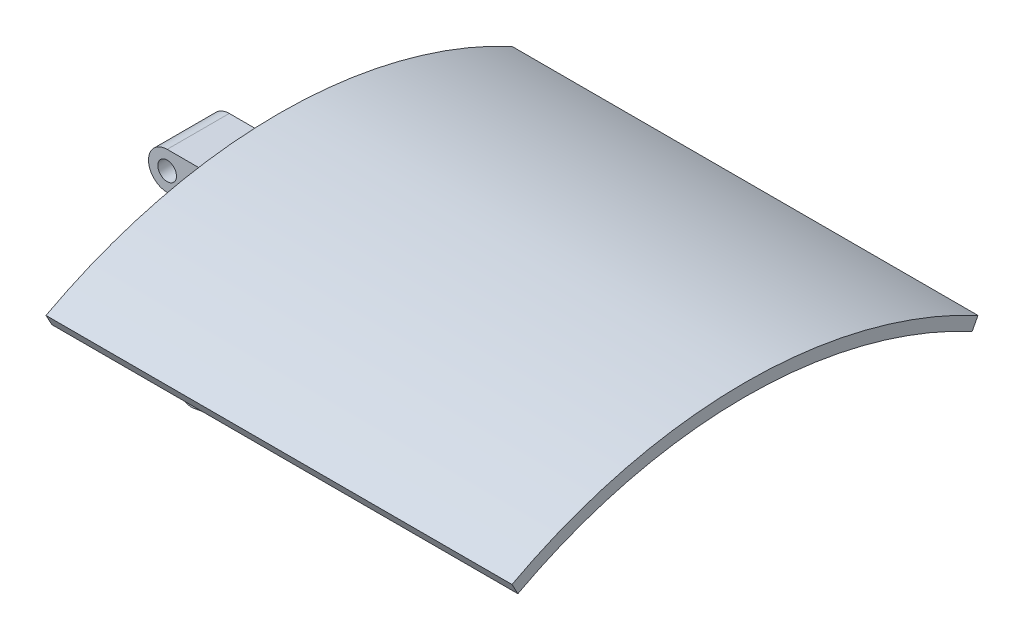
SolidWorks part; units mm, degrees
ref_plane "Plan de face" through (0, 0, 0) normal (0, 0, 1) x (1, 0, 0)
ref_plane "Plan de dessus" through (0, 0, 0) normal (0, 1, 0) x (1, 0, 0)
ref_plane "Plan de droite" through (0, 0, 0) normal (1, 0, 0) x (0, 0, -1)
sketch "Esquisse1" plane through (0, 0, 0) normal (1, 0, 0) x (0, 0, -1)
  line L0 (-37.5, 70.0999) -> (0, 0) construction
  line L1 (0, 0) -> (37.5, 70.0999) construction
  line L2 (-37.5, 70.0999) -> (37.5, 70.0999) construction
  line L3 (0, 70.0999) -> (0, 0) construction
  line L4 (-37.5, 70.0999) -> (-36.5566, 68.3364)
  line L5 (37.5, 70.0999) -> (36.5566, 68.3364)
  arc A0 (-37.5, 70.0999) -> (37.5, 70.0999) centre (0, 0) cw
  arc A1 (-36.5566, 68.3364) -> (36.5566, 68.3364) centre (0, 0) cw
  dimension "D1" = 77.5
  dimension "D2" = 56.289
  dimension "D3" = 2
  dimension "D4" = 75
extrude "Boss.-Extru.1" add sketch "Esquisse1" along normal blind 75
sketch "Esquisse7" plane through (0, 0, 0) normal (0, 0, 1) x (1, 0, 0)
  line L0 (7, 77.5) -> (7, 70.5)
  line L1 (75, 77.5) -> (0, 77.5) construction
  line L2 (7, 77.5) -> (13, 77.5)
  line L3 (13, 77.5) -> (13, 64.5)
  line L5 (13, 64.5) -> (-13, 64.5)
  line L6 (-13, 64.5) -> (-13, 70.5) construction
  line L7 (-13, 70.5) -> (7, 70.5)
  line L10 (10, 77.5) -> (0, 77.5) construction
  line L11 (-13, 67.5) -> (7, 67.5) construction
  line L12 (7, 67.5) -> (7, 70.5) construction
  line L13 (7, 67.5) -> (7, 64.5) construction
  line L14 (7, 70.5) -> (-1.6824, 119.7404) construction
  circle A0 centre (-13, 67.5) radius 1.5
  arc A1 (-13, 70.5) -> (-13, 64.5) centre (-13, 67.5) ccw
  dimension "D3" = 3
  dimension "D1" = 6
  dimension "D2" = 10
  dimension "D4" = 23
  dimension "D5" = 10
  dimension "D6" = 80
  dimension "D7" = 50
extrude "Boss.-Extru.3" add sketch "Esquisse7" along normal blind 5 and the other way blind 5 contours L7 L0 L2 L3 L5 A1 | A0
sketch "Esquisse3" plane through (0, 0, 0) normal (0, 0, 1) x (1, 0, 0)
  line L0 (30.7214, 77.5) -> (30.7214, 72.5)
  line L1 (75, 77.5) -> (13, 77.5) construction
  line L2 (30.7214, 72.5) -> (36.7214, 72.5) construction
  line L3 (36.7214, 72.5) -> (36.7214, 77.5)
  line L4 (36.7214, 77.5) -> (30.7214, 77.5)
  line L5 (-74.1468, 29.3655) -> (-127.2256, 20.0063) construction
  line L6 (-73.1207, 23.5464) -> (-132.9596, 12.9952) construction
  line L7 (-11, 40.5) -> (-11, 34.5) construction
  line L8 (-13, 67.5) -> (-11, 67.5) construction
  line L9 (36.7214, -12.0757) -> (36.7214, -21.0592) construction
  line L10 (30.7214, 72.5) -> (36.7214, 72.5) construction
  line L11 (30.7214, -123.9412) -> (30.7214, -122.8027) construction
  line L12 (72.7696, 84.9142) -> (60.2573, 82.708) construction
  line L13 (132.8929, 62.8722) -> (91.2136, 55.523) construction
  line L14 (123.3905, 91.5493) -> (80.4346, 83.975) construction
  line L15 (-13, 67.5) -> (-7.8094, 38.0626) construction
  line L16 (-11, 37.5) -> (-16.5823, 69.1591) construction
  line L17 (-13, 67.5) -> (-11, 37.5) construction
  line L18 (-11, 37.5) -> (33.7214, 77.5) construction
  line L19 (33.7214, 77.5) -> (-13, 67.5) construction
  line L20 (30.7214, 77.5) -> (-13, 77.5) construction
  line L21 (-13, 77.5) -> (-13, 67.5) construction
  line L22 (-11, 67.5) -> (-11, 37.5) construction
  arc A0 (-11, 40.5) -> (-11, 34.5) centre (-11, 37.5) ccw
  circle A1 centre (-11, 37.5) radius 1.5
  arc A2 (-11, 34.5) -> (36.7214, 72.5) centre (-2.2688, 72.5) ccw construction
  arc A3 (-11, 40.5) -> (30.7214, 72.5) centre (-2.4112, 72.5) ccw construction
  spline S0 degree 3 poles (30.7214, 72.5) (30.7214, 44.695) (24.9104, 46.832) (-11, 40.5) knots 0 0 0 0 1 1 1 1
  spline S1 degree 3 poles (36.7214, 72.5) (36.7214, 41.4065) (28.3973, 41.4468) (-11, 34.5) knots 0 0 0 0 1 1 1 1
  text T0 "A"
  text T1 "C"
  text T2 "B"
  text T3 "B'"
  point P27 (-13, 67.5)
  dimension "D4" = 3
  dimension "D5" = 12.081
  dimension "D2" = 5
  dimension "D3" = 6
  dimension "D6" = 10
  dimension "D7" = 3.2398
  dimension "D8" = 60
  dimension "D9" = 2
  dimension "D10" = 30.0666
  dimension "D11" = 40
  dimension "D12" = 47.7796
extrude "Boss.-Extru.2" add sketch "Esquisse3" along normal blind 3 and the other way blind 3 contours L3 L4 L0 S0 A0 S1 | A1
ref_plane "Plan2" through (0, 67.5, 0) normal (0, 1, 0) x (1, 0, 0)
ref_plane "Plan3" through (0, 0, 0) normal (0, 0, 1) x (1, 0, 0)
ref_plane "Plan4" through (0, 79.5, 0) normal (0, 1, 0) x (1, 0, 0)
sketch "Esquisse8" plane through (0, 79.5, 0) normal (0, 1, 0) x (1, 0, 0)
  line L0 (30.7214, -3) -> (36.7214, -3) construction
  line L1 (30.7214, 3) -> (30.7214, -3) construction
  line L2 (30.7214, 3) -> (36.7214, 3) construction
  line L3 (30.7214, -3) -> (36.7214, -3) construction
  line L4 (30.7214, 3) -> (30.7214, -3) construction
  line L5 (30.7214, 3) -> (36.7214, 3) construction
  line L6 (36.7214, -3) -> (36.7214, 3) construction
  line L7 (36.7214, -3) -> (36.7214, 3) construction
  line L8 (30.7214, -3) -> (36.7214, 3) construction
  line L9 (30.7214, 3) -> (36.7214, -3) construction
  point P3 (33.7214, 0)
sketch "Esquisse9" plane through (0, 0, 0) normal (0, 0, 1) x (1, 0, 0)
  line L0 (-11, 37.5) -> (-13, 67.5) construction
  line L1 (-13, 67.5) -> (33.7214, 79.5) construction
  line L2 (33.7214, 79.5) -> (-11, 37.5) construction
  line L3 (75, 79.5) -> (0, 79.5) construction
  line L4 (75, 79.5) -> (0, 79.5) construction
  line L5 (-13, 67.5) -> (-13, 79.5) construction
  line L6 (-13, 79.5) -> (0, 79.5) construction
  point P0 (-13, 67.5)
  point P1 (-11, 37.5)
  dimension "D1" = 50.611
  dimension "D2" = 28.798
  dimension "D3" = 100.591
  dimension "D4" = 14.405
